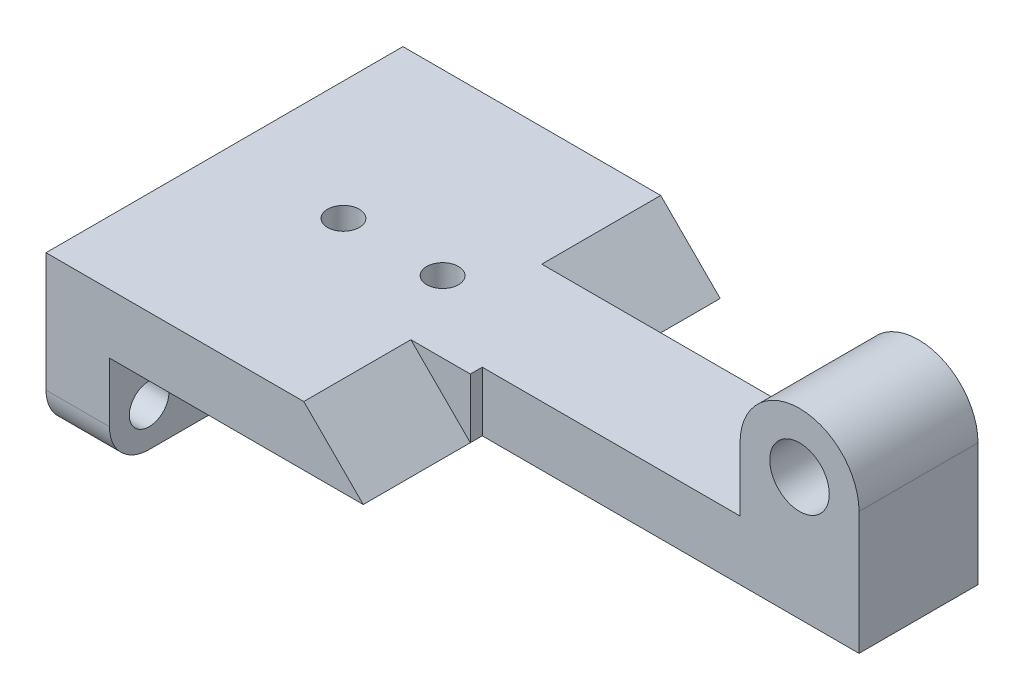
SolidWorks part; units mm, degrees
ref_plane "Front Plane" through (0, 0, 0) normal (0, 0, 1) x (1, 0, 0)
ref_plane "Top Plane" through (0, 0, 0) normal (0, 1, 0) x (1, 0, 0)
ref_plane "Right Plane" through (0, 0, 0) normal (1, 0, 0) x (0, 0, -1)
sketch "Sketch1" plane through (0, 0, 0) normal (0, 0, 1) x (1, 0, 0)
  line L0 (0, 15) -> (0, -25)
  line L1 (0, -25) -> (16, -25)
  line L2 (16, -25) -> (16, 0)
  line L3 (16, 0) -> (175, 0)
  line L4 (175, 0) -> (175, 31)
  line L5 (145, 31) -> (145, 15)
  line L6 (145, 15) -> (0, 15)
  line L7 (65, 15) -> (80, 0)
  line L8 (80, 0) -> (80, 15)
  arc A0 (175, 31) -> (145, 31) centre (160, 31) ccw
  circle A1 centre (160, 31) radius 7.5
  dimension "D1" = 16
  dimension "D3" = 15
  dimension "D4" = 30
  dimension "D2" = 16
  dimension "D5" = 15
  dimension "D6" = 40
  dimension "D7" = 175
  dimension "D8" = 45
  dimension "D9" = 80
extrude "Boss-Extrude1" add sketch "Sketch1" along normal mid plane 30 contours L4 A0 L5 L6 L7 L3 A1 region at (137.7527, 14.1497, 0)
extrude "Boss-Extrude2" add sketch "Sketch1<3>" along normal mid plane 90 contours L7 L6 L0 L1 L2 L3 region at (28.7479, 1.9328, 0)
sketch "Sketch1<3>" plane through (0, 0, 0) normal (0, 0, 1) x (1, 0, 0) same geometry as "Sketch1"
sketch "Sketch2" plane through (0, 15, 0) normal (0, 1, 0) x (1, 0, 0)
  line L0 (0, -45) -> (0, 45) construction
  circle A0 centre (55, 0) radius 4
  circle A1 centre (30, 0) radius 4
  dimension "D1" = 8
  dimension "D2" = 8
  dimension "D3" = 25
  dimension "D4" = 30
extrude "Boss-Extrude3" add sketch "Sketch1<4>" along normal blind 18 and the other way blind 15 contours L7 L8 L6 region at (75, 10, 0)
sketch "Sketch1<4>" plane through (0, 0, 0) normal (0, 0, 1) x (1, 0, 0) same geometry as "Sketch1"
extrude "Cut-Extrude1" cut sketch "Sketch2" against normal up to next
sketch "Sketch3" plane through (0, 0, 0) normal (-1, 0, 0) x (0, 0, 1)
  line L0 (0, 3.4748) -> (0, -4.318) construction
  line L1 (45, 15) -> (45, -25) construction
  line L2 (45, -25) -> (-45, -25) construction
  circle A0 centre (35, -15) radius 5
  circle A1 centre (35, -15) radius 10
  circle A4 centre (-35, -15) radius 10
  circle A5 centre (-35, -15) radius 5
  line M3 (-45, 15) -> (-45, -25)
  line M4 (-45, -25) -> (45, -25)
  line M5 (45, -25) -> (45, 15)
  dimension "D1" = 10
  dimension "D2" = 20
extrude "Cut-Extrude2" cut sketch "Sketch3" against normal up to next contours A0 | A1 M4 M5 | A5 | A4 M4 M3 region at (0, -15, 35) region at (0, -22.7663, 42.7663) region at (0, -22.7663, -42.7663) region at (0, -15, -35)
